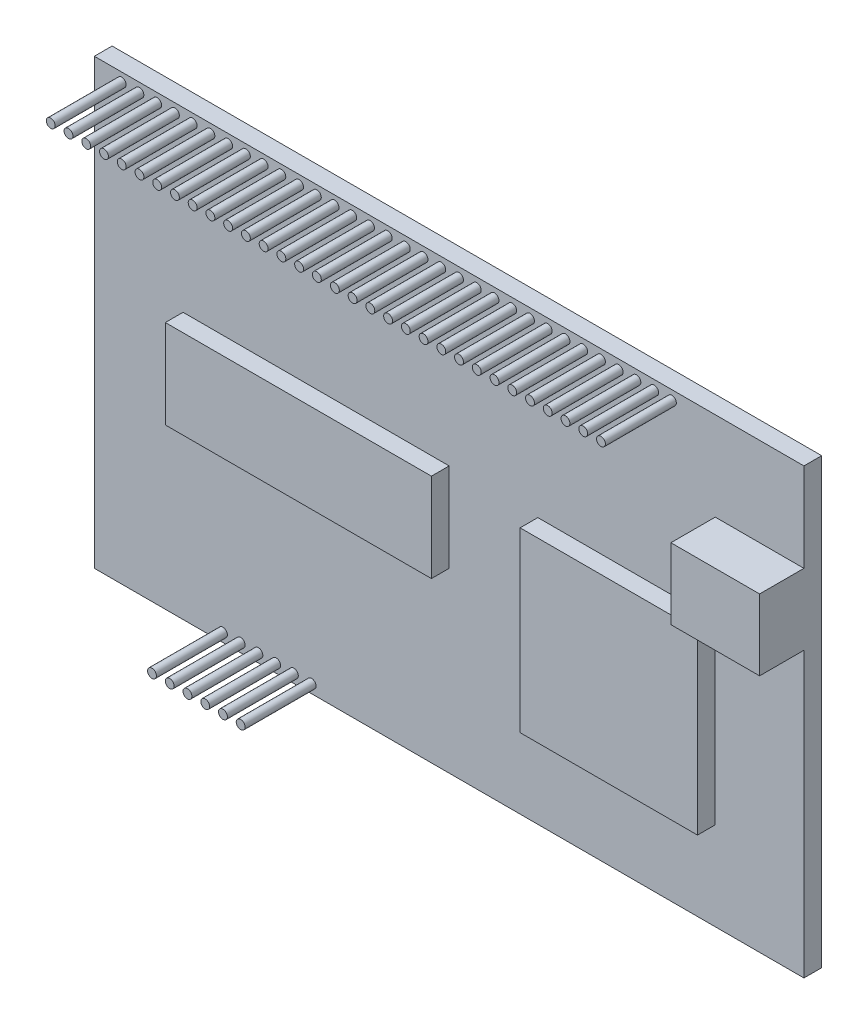
SolidWorks part; units mm, degrees
ref_plane "Front Plane" through (0, 0, 0) normal (0, 0, 1) x (1, 0, 0)
ref_plane "Top Plane" through (0, 0, 0) normal (0, 1, 0) x (1, 0, 0)
ref_plane "Right Plane" through (0, 0, 0) normal (1, 0, 0) x (0, 0, -1)
sketch "Sketch1" plane through (0, 0, 0) normal (0, 0, 1) x (1, 0, 0)
  line L0 (-28.8497, 40.0449) -> (-28.8497, -9.9551)
  line L1 (-28.8497, -9.9551) -> (51.1503, -9.9551)
  line L2 (51.1503, -9.9551) -> (51.1503, 40.0449)
  line L3 (51.1503, 40.0449) -> (-28.8497, 40.0449)
  line L4 (-18.8497, 20.0449) -> (-18.8497, 10.0449)
  line L5 (-18.8497, 10.0449) -> (11.1503, 10.0449)
  line L6 (11.1503, 10.0449) -> (11.1503, 20.0449)
  line L7 (11.1503, 20.0449) -> (-18.8497, 20.0449)
  line L8 (21.1503, 20) -> (21.1503, 0)
  line L9 (21.1503, 0) -> (41.1503, 0)
  line L10 (41.1503, 0) -> (41.1503, 20)
  line L11 (41.1503, 20) -> (21.1503, 20)
  line L12 (51.1503, 30.0449) -> (41.1503, 30.0449)
  line L13 (41.1503, 30.0449) -> (41.1503, 22.0449)
  line L14 (41.1503, 22.0449) -> (51.1503, 22.0449)
  circle A0 centre (-25.7677, 39.0449) radius 0.5
  circle A1 centre (-23.7677, 39.0449) radius 0.5
  circle A2 centre (-21.7677, 39.0449) radius 0.5
  circle A3 centre (-19.7677, 39.0449) radius 0.5
  circle A4 centre (-17.7677, 39.0449) radius 0.5
  circle A5 centre (-15.7677, 39.0449) radius 0.5
  circle A6 centre (-13.7677, 39.0449) radius 0.5
  circle A7 centre (-11.7677, 39.0449) radius 0.5
  circle A8 centre (-14.3548, -8.9551) radius 0.5
  circle A9 centre (-12.3548, -8.9551) radius 0.5
  circle A10 centre (-10.3548, -8.9551) radius 0.5
  circle A11 centre (-8.3548, -8.9551) radius 0.5
  circle A12 centre (-6.3548, -8.9551) radius 0.5
  circle A13 centre (-4.3548, -8.9551) radius 0.5
  circle A16 centre (-9.7677, 39.0449) radius 0.5
  circle A17 centre (-7.7677, 39.0449) radius 0.5
  circle A18 centre (-5.7677, 39.0449) radius 0.5
  circle A19 centre (-3.7677, 39.0449) radius 0.5
  circle A20 centre (-1.7677, 39.0449) radius 0.5
  circle A21 centre (0.2323, 39.0449) radius 0.5
  circle A22 centre (2.2323, 39.0449) radius 0.5
  circle A23 centre (4.2323, 39.0449) radius 0.5
  circle A24 centre (6.2642, 38.9964) radius 0.5
  circle A25 centre (8.2642, 38.9964) radius 0.5
  circle A26 centre (10.2642, 38.9964) radius 0.5
  circle A27 centre (12.2642, 38.9964) radius 0.5
  circle A28 centre (14.2642, 38.9964) radius 0.5
  circle A29 centre (16.2642, 38.9964) radius 0.5
  circle A30 centre (18.2642, 38.9964) radius 0.5
  circle A31 centre (20.2642, 38.9964) radius 0.5
  circle A32 centre (22.2642, 38.9964) radius 0.5
  circle A33 centre (24.2642, 38.9964) radius 0.5
  circle A34 centre (26.2642, 38.9964) radius 0.5
  circle A35 centre (28.2642, 38.9964) radius 0.5
  circle A36 centre (30.2642, 38.9964) radius 0.5
  circle A37 centre (32.2642, 38.9964) radius 0.5
  circle A38 centre (34.2642, 38.9964) radius 0.5
  circle A39 centre (36.2642, 38.9964) radius 0.5
  point P61 (0, 0)
  point P62 (0, 0)
  point P64 (-12.0648, 39.1346)
  dimension "D1" = 1
  dimension "D2" = 1
  dimension "D3" = 1
  dimension "D4" = 1
  dimension "D5" = 1
  dimension "D6" = 1
  dimension "D7" = 1
  dimension "D8" = 1
  dimension "D50" = 1
  dimension "D51" = 1
  dimension "D52" = 1
  dimension "D9" = 2
  dimension "D10" = 2
  dimension "D11" = 2
  dimension "D12" = 2
  dimension "D13" = 2
  dimension "D14" = 2
  dimension "D15" = 2
  dimension "D16" = 1
  dimension "D17" = 1
  dimension "D18" = 1
  dimension "D19" = 1
  dimension "D20" = 1
  dimension "D21" = 1
  dimension "D22" = 80
  dimension "D23" = 50
  dimension "D24" = 30
  dimension "D25" = 10
  dimension "D26" = 20
  dimension "D27" = 1
  dimension "D28" = 20
  dimension "D29" = 20
  dimension "D30" = 10
  dimension "D31" = 8
  dimension "D32" = 10
  dimension "D33" = 10
  dimension "D34" = 1
  dimension "D35" = 2
  dimension "D36" = 2
  dimension "D37" = 1
  dimension "D38" = 1
  dimension "D39" = 1
  dimension "D40" = 1
  dimension "D41" = 1
  dimension "D42" = 1
  dimension "D43" = 1
  dimension "D44" = 2
  dimension "D45" = 2
  dimension "D46" = 2
  dimension "D47" = 2
  dimension "D48" = 2
  dimension "D49" = 2
  dimension "D53" = 2
  dimension "D54" = 2
  dimension "D55" = 2
  dimension "D56" = 2
  dimension "D57" = 2
  dimension "D58" = 2
  dimension "D59" = 2
  dimension "D60" = 2
  dimension "D61" = 2
  dimension "D62" = 2
  dimension "D63" = 2
  dimension "D64" = 10
extrude "Boss-Extrude1" add sketch "Sketch1" along normal blind 2 contours L14 L13 L12 L2 L3 L0 L1 A13 A12 A11 A10 A9 A8 A7 A6 A5 A4 A3 A2 A1 A0 L11 L10 L9 L8 L7 L6 L5 L4 region at (11.1503, 39.1015, 0)
extrude "Boss-Extrude2" add sketch "Sketch1<3>" along normal blind 10 contours A0 | A1 | A3 | A2 | A4 | A5 | A6 | A7 | A8 | A9 | A10 | A11 | A12 | A13 | A16 | A17 | A18 | A19 | A20 | A22 | A21 | A23 | A24 | A25 | A26 | A27 | A28 | A29 | A30 | A31 | A32 | A33 | A34 | A35 | A36 | A37 | A39 | A38 region at (-25.7677, 39.0449, 0) region at (-23.7677, 39.0449, 0) region at (-21.7677, 39.0449, 0) region at (-19.7677, 39.0449, 0) region at (-17.7677, 39.0449, 0) region at (-15.7677, 39.0449, 0) region at (-13.7677, 39.0449, 0) region at (-11.7677, 39.0449, 0) region at (-14.3548, -8.9551, 0) region at (-12.3548, -8.9551, 0) region at (-10.3548, -8.9551, 0) region at (-8.3548, -8.9551, 0) region at (-6.3548, -8.9551, 0) region at (-4.3548, -8.9551, 0)
sketch "Sketch1<3>" plane through (0, 0, 0) normal (0, 0, 1) x (1, 0, 0) same geometry as "Sketch1"
extrude "Boss-Extrude3" add sketch "Sketch1<4>" along normal blind 4 contours L6 L7 L4 L5 | L10 L11 L8 L9 region at (-3.8497, 15.0449, 0) region at (31.1503, 10, 0)
sketch "Sketch1<4>" plane through (0, 0, 0) normal (0, 0, 1) x (1, 0, 0) same geometry as "Sketch1"
extrude "Boss-Extrude4" add sketch "Sketch1<5>" along normal blind 7 contours L13 L14 L2 L12 region at (46.1503, 26.0449, 0)
sketch "Sketch1<5>" plane through (0, 0, 0) normal (0, 0, 1) x (1, 0, 0) same geometry as "Sketch1"
